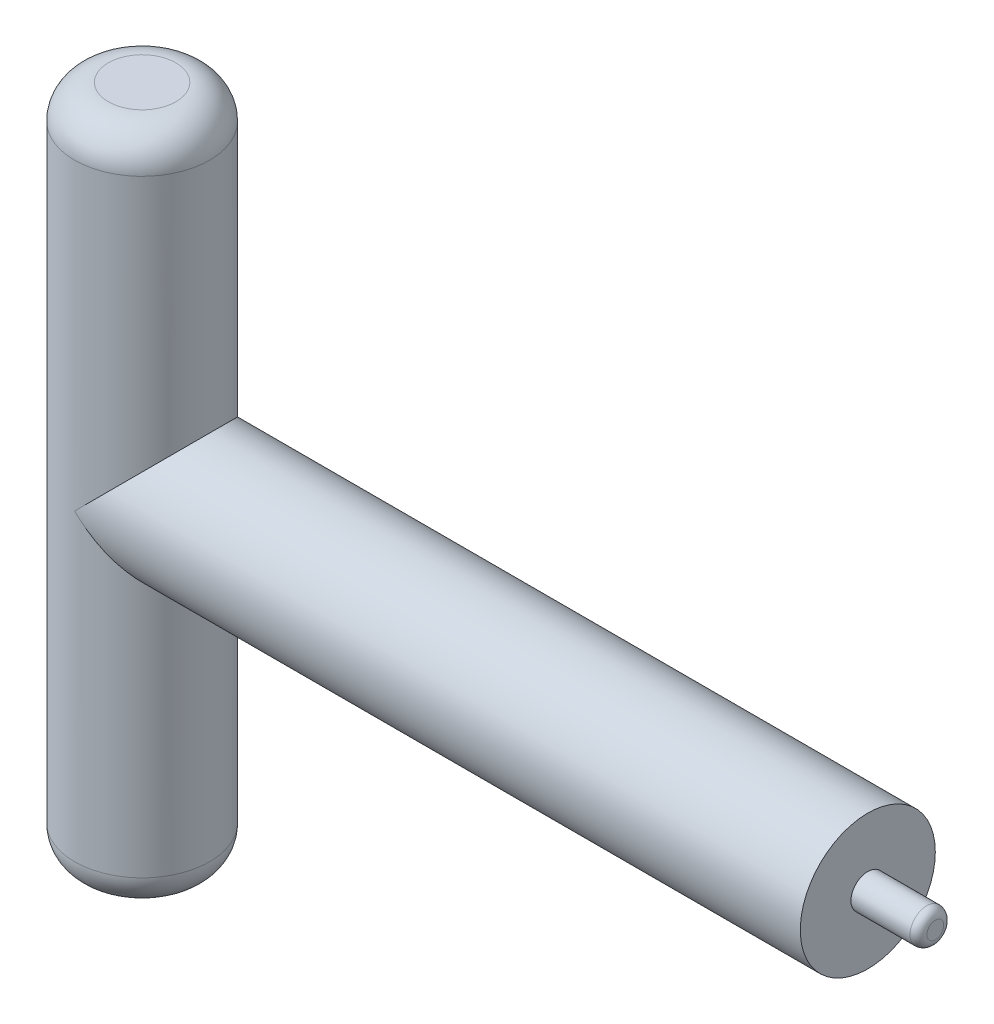
SolidWorks part; units mm, degrees
material "AISI 304"
ref_plane "Front" through (0, 0, 0) normal (0, 0, 1) x (1, 0, 0)
ref_plane "Top" through (0, 0, 0) normal (0, 1, 0) x (1, 0, 0)
ref_plane "Right" through (0, 0, 0) normal (1, 0, 0) x (0, 0, -1)
sketch "Sketch1" plane through (0, 0, 0) normal (1, 0, 0) x (0, 0, -1)
  circle A0 centre (0, 0) radius 12.7
  dimension "D1" = 25.4
extrude "Boss-Extrude1" add sketch "Sketch1" along normal blind 136.525
sketch "Sketch2" plane through (136.525, 0, 0) normal (1, 0, 0) x (0, 0, -1)
  circle A0 centre (0, 0) radius 3.175
  dimension "D1" = 6.35
extrude "Boss-Extrude2" add sketch "Sketch2" along normal blind 12.7
fillet "Fillet2" radius 1.5875 1 edges at (149.225, 0, -3.175)
sketch "Sketch3" plane through (0, 0, 0) normal (0, 1, 0) x (1, 0, 0)
  circle A0 centre (0, 0) radius 12.7
  dimension "D1" = 25.4
extrude "Boss-Extrude3" add sketch "Sketch3" along normal blind 63.5 and the other way blind 63.5
fillet "Fillet3" radius 6.35 2 edges at (0, 63.5, 12.7) (0, -63.5, 12.7)
